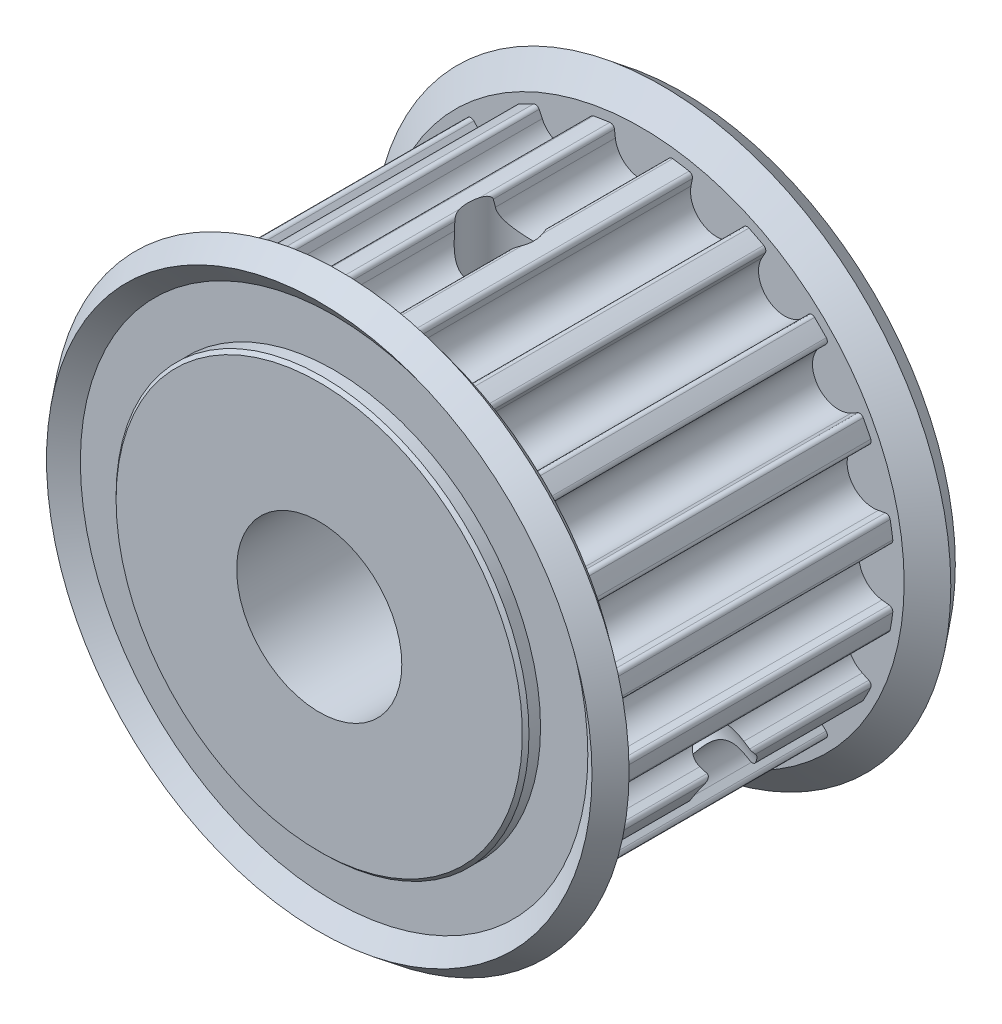
SolidWorks part; units mm, degrees
ref_plane "前视基准面" through (0, 0, 0) normal (0, 0, 1) x (1, 0, 0)
ref_plane "上视基准面" through (0, 0, 0) normal (0, 1, 0) x (1, 0, 0)
ref_plane "右视基准面" through (0, 0, 0) normal (1, 0, 0) x (0, 0, -1)
sketch "草图1" plane through (0, 0, 0) normal (1, 0, 0) x (0, 0, -1)
  line L0 (-34.7811, 0) -> (33.6192, 0) construction
  line L1 (0, 52.9736) -> (0, -62.0281) construction
  line L2 (-8.5, 15.345) -> (-8.5, 15.915)
  line L3 (-8.5, 15.915) -> (-9.7397, 17.5)
  line L4 (-9.7397, 17.5) -> (-11, 16.5143)
  line L5 (-11, 16.5143) -> (-10.1, 15.3636)
  line L6 (-10.1, 15.3636) -> (-10.1, 12.5)
  line L7 (-10.1, 12.5) -> (-11, 12.5)
  line L8 (10.1, 12.5) -> (11, 12.5)
  line L9 (10.1, 15.3636) -> (10.1, 12.5)
  line L10 (11, 16.5143) -> (10.1, 15.3636)
  line L11 (9.7397, 17.5) -> (11, 16.5143)
  line L12 (8.5, 15.915) -> (9.7397, 17.5)
  line L13 (8.5, 15.345) -> (8.5, 15.915)
  line L14 (8.5, -15.345) -> (8.5, -15.915)
  line L15 (8.5, -15.915) -> (9.7397, -17.5)
  line L16 (9.7397, -17.5) -> (11, -16.5143)
  line L17 (11, -16.5143) -> (10.1, -15.3636)
  line L18 (10.1, -15.3636) -> (10.1, -12.5)
  line L19 (10.1, -12.5) -> (11, -12.5)
  line L20 (-10.1, -12.5) -> (-11, -12.5)
  line L21 (-10.1, -15.3636) -> (-10.1, -12.5)
  line L22 (-11, -16.5143) -> (-10.1, -15.3636)
  line L23 (-9.7397, -17.5) -> (-11, -16.5143)
  line L24 (-8.5, -15.915) -> (-9.7397, -17.5)
  line L25 (-8.5, -15.345) -> (-8.5, -15.915)
  line L26 (-11, 12.5) -> (-11, -12.5)
  line L27 (11, 12.5) -> (11, -12.5)
  line L28 (-8.5, 15.345) -> (8.5, 15.345)
  line L29 (-8.5, -15.345) -> (8.5, -15.345)
  point P33 (0, 15.345)
  dimension "D1" = 2.5
  dimension "F" = 35
  dimension "D2" = 1.6
  dimension "E" = 25
  dimension "D3" = 1.6
  dimension "W" = 22
  dimension "D4" = 31.83
  dimension "A" = 17
  dimension "D5" = 30.69
sketch "草图2" plane through (0, 0, 0) normal (0, 0, 1) x (1, 0, 0)
  line L0 (-18.7064, 0) -> (19.5832, 0) construction
  line L1 (0, 30.5033) -> (0, -25.8377) construction
  line L2 (0, 0) -> (0, 15.345) construction
  line L3 (1.5718, 14.5756) -> (1.625, 15.0088)
  line L7 (0, 52.9736) -> (0, -62.0281) construction
  line L8 (-1.5, 3.7081) -> (-1.5, 5.4)
  line L9 (1.5, 3.7081) -> (1.5, 5.4)
  line L10 (-1.5, 5.4) -> (1.5, 5.4)
  line L11 (-1.5718, 14.5756) -> (-1.625, 15.0088)
  circle A0 centre (0, 0) radius 15.345
  circle A1 centre (0, 0) radius 15.915 construction
  circle A6 centre (0, 0) radius 2.5
  circle A7 centre (0, 0) radius 4
  arc A11 (-1.5718, 14.5756) -> (1.5718, 14.5756) centre (0, 14.7686) ccw
  arc A12 (-1.625, 15.0088) -> (-1.9042, 15.2264) centre (-1.8731, 14.9783) ccw
  arc A13 (1.625, 15.0088) -> (1.9042, 15.2264) centre (1.8731, 14.9783) cw
  point P7 (0, 15.915)
  point P8 (0, 15.345)
  point P13 (15.345, 0)
  dimension "PD" = 31.83
  dimension "OD" = 30.69
  dimension "H" = 5
  dimension "N" = 8
  dimension "D3" = 0.5
  dimension "D4" = 2.16
  dimension "D5" = 3.25
  dimension "D1" = 7
  dimension "b" = 3
  dimension "t" = 1.4
sketch "草图3" plane through (0, 0, 0) normal (1, 0, 0) x (0, 0, -1)
  line L0 (-11, 12.5) -> (-11, -12.5) construction
  line L1 (11, 12.5) -> (11, -12.5) construction
  line L2 (11, 16.5143) -> (10.1, 15.3636) construction
  line L3 (10.1, 12.5) -> (11, 12.5) construction
  line L4 (10.1, 15.3636) -> (10.1, 12.5) construction
  line L5 (-10.1, 15.3636) -> (-10.1, 12.5) construction
  line L6 (-11, 12.5) -> (-11, 0)
  line L7 (11, 12.5) -> (11, 0)
  line L8 (9.7397, 17.5) -> (11, 16.5143) construction
  line L9 (10.1, 12.5) -> (11, 12.5)
  line L10 (10.1, 15.3636) -> (10.1, 12.5)
  line L11 (-10.1, 15.3636) -> (-10.1, 12.5)
  line L12 (8.5, 15.915) -> (9.7397, 17.5) construction
  line L13 (8.5, 15.345) -> (8.5, 15.915) construction
  line L14 (-8.5, 15.345) -> (8.5, 15.345) construction
  line L15 (-8.5, 15.345) -> (-8.5, 15.915) construction
  line L16 (-8.5, 15.915) -> (-9.7397, 17.5) construction
  line L17 (-9.7397, 17.5) -> (-11, 16.5143) construction
  line L18 (-11, 16.5143) -> (-10.1, 15.3636) construction
  line L19 (11, 16.5143) -> (10.1, 15.3636)
  line L20 (9.7397, 17.5) -> (11, 16.5143)
  line L21 (8.5, 15.915) -> (9.7397, 17.5)
  line L22 (8.5, 15.345) -> (8.5, 15.915)
  line L23 (-8.5, 15.345) -> (8.5, 15.345)
  line L24 (-8.5, 15.345) -> (-8.5, 15.915)
  line L25 (-8.5, 15.915) -> (-9.7397, 17.5)
  line L26 (-9.7397, 17.5) -> (-11, 16.5143)
  line L27 (-11, 16.5143) -> (-10.1, 15.3636)
  line L28 (-34.7811, 0) -> (33.6192, 0) construction
  line L29 (-34.7811, 0) -> (33.6192, 0) construction
  line L30 (-11, 0) -> (11, 0)
  line L31 (-10.1, 12.5) -> (-11, 12.5) construction
  line L32 (-10.1, 12.5) -> (-11, 12.5)
revolve "旋转1" add sketch "草图3" angle 360 about L29
sketch "草图4" plane through (0, 0, 0) normal (0, 0, 1) x (1, 0, 0)
  line L3 (-1.5718, 14.5756) -> (-1.625, 15.0088) construction
  line L4 (1.5718, 14.5756) -> (1.625, 15.0088) construction
  line L5 (-1.5718, 14.5756) -> (-1.625, 15.0088)
  line L6 (1.5718, 14.5756) -> (1.625, 15.0088)
  arc A5 (-1.625, 15.0088) -> (-1.9042, 15.2264) centre (-1.8731, 14.9783) ccw construction
  arc A6 (-1.5718, 14.5756) -> (1.5718, 14.5756) centre (0, 14.7686) ccw construction
  arc A7 (1.9042, 15.2264) -> (1.625, 15.0088) centre (1.8731, 14.9783) ccw construction
  circle A8 centre (0, 0) radius 15.345 construction
  arc A9 (-1.625, 15.0088) -> (-1.9042, 15.2264) centre (-1.8731, 14.9783) ccw
  arc A10 (-1.5718, 14.5756) -> (1.5718, 14.5756) centre (0, 14.7686) ccw
  arc A11 (1.9042, 15.2264) -> (1.625, 15.0088) centre (1.8731, 14.9783) ccw
  arc A12 (1.9042, 15.2264) -> (-1.9042, 15.2264) centre (0, 0) ccw
extrude "切除-拉伸1" cut sketch "草图4" along normal up to vertex (8.5 mm away) from vertex up to point (0, 15.345, 8.5) starting at point (0, 15.345, -8.5)
pattern_circular "阵列(圆周)1" count 20 over 360 about axis through (0, 0, 34.7811) along (0, 0, 1) of "切除-拉伸1"
sketch "草图5" plane through (0, 0, 0) normal (0, 0, 1) x (1, 0, 0)
  circle A0 centre (0, 0) radius 2.5 construction
  circle A1 centre (0, 0) radius 2.5
extrude "H" [suppressed] cut sketch "草图5" along normal up to vertex from vertex up to point (0, 12.5, 11) starting at point (0, 12.5, -11)
sketch "草图6" plane through (0, 0, 0) normal (0, 0, 1) x (1, 0, 0)
  line L3 (-1.875, 6.327) -> (1.875, 6.327)
  line L4 (1.875, 4.6351) -> (1.875, 6.327)
  line L5 (-1.875, 4.6351) -> (-1.875, 6.327)
  arc A1 (-1.875, 4.6351) -> (1.875, 4.6351) centre (0, 0) ccw
  dimension "D1" = 5
extrude "N" cut sketch "草图6" along normal up to vertex (11 mm away) from vertex up to point (0, 12.5, 11) starting at point (0, 12.5, -11)
sketch "草图8" plane through (0, 0, 0) normal (0, 0, 1) x (1, 0, 0)
  line L3 (-1.875, 4.6351) -> (-1.875, 6.327)
  line L4 (-1.875, 6.327) -> (1.875, 6.327)
  line L5 (1.875, 4.6351) -> (1.875, 6.327)
  line L6 (1.875, 6.327) -> (-1.875, 6.327) construction
  line L7 (-1.875, 6.327) -> (-1.875, 4.6351) construction
  line L8 (1.875, 4.6351) -> (1.875, 6.327) construction
  arc A1 (1.875, 4.6351) -> (-1.875, 4.6351) centre (0, 0) ccw
  arc A2 (-1.875, 4.6351) -> (1.875, 4.6351) centre (0, 0) ccw construction
extrude "P" add sketch "草图8" against normal up to vertex from vertex up to point (0, 12.5, -11) starting at point (0, 12.5, 11)
sketch "草图7" plane through (0, 0, 0) normal (0, 1, 0) x (1, 0, 0)
  circle A0 centre (0, 0) radius 2
  dimension "M" = 4
extrude "螺纹孔1" cut sketch "草图7" along normal up to vertex up to point (0, 15.345, 0)
cosmetic thread "装饰螺纹线1" parameters "D2"=4.1
pattern_circular "螺纹孔2" count 2 every 120 about axis through (0, 0, 34.7811) along (0, 0, 1) of "螺纹孔1" reverse direction yes
chamfer "倒角1" distance 0.2 angle 45 2 edges at (12.5, 0, -11) (12.5, 0, 11)
